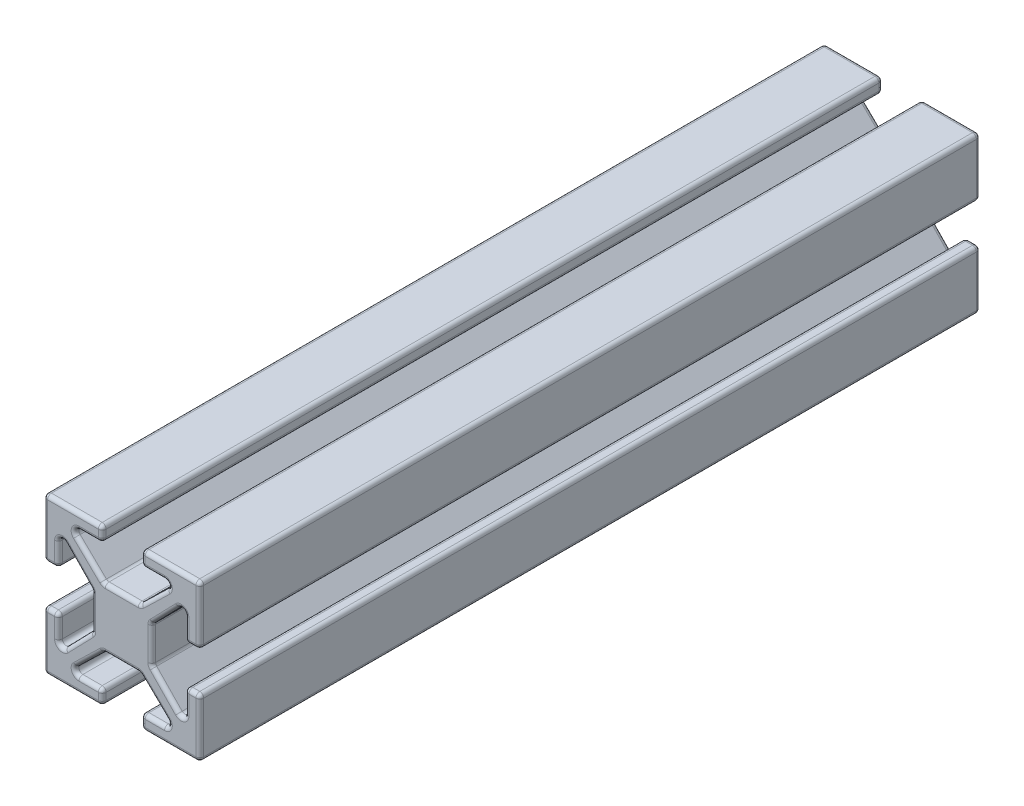
SolidWorks part; units mm, degrees
ref_plane "Front Plane" through (0, 0, 0) normal (0, 0, 1) x (1, 0, 0)
ref_plane "Top Plane" through (0, 0, 0) normal (0, 1, 0) x (1, 0, 0)
ref_plane "Right Plane" through (0, 0, 0) normal (1, 0, 0) x (0, 0, -1)
sketch "Sketch1" plane through (0, 0, 0) normal (0, 0, 1) x (1, 0, 0)
  line L0 (-5, 20) -> (-5, 16.2126)
  line L1 (-20, -20) -> (20, -20)
  line L2 (-20, -20) -> (-20, 20)
  line L3 (-20, 20) -> (20, 20)
  line L4 (20, -20) -> (20, 20)
  line L5 (-20, -20) -> (20, 20) construction
  line L6 (-20, 20) -> (20, -20) construction
  line L7 (-5, 16.2126) -> (-13.4323, 16.2126)
  line L8 (-13.4323, 16.2126) -> (-4.6312, 7.6894)
  line L9 (-4.6312, 7.6894) -> (0, 7.6894)
  line L10 (-7.6894, 4.6312) -> (-7.6894, 0)
  line L11 (-16.2126, 13.4323) -> (-7.6894, 4.6312)
  line L12 (-16.2126, 5) -> (-16.2126, 13.4323)
  line L13 (-20, 5) -> (-16.2126, 5)
  line L14 (0, 7.6894) -> (0, 16.8611) construction
  line L15 (0, 0) -> (-11.384, 0) construction
  line L16 (5, 20) -> (5, 16.2126)
  line L17 (5, 16.2126) -> (13.4323, 16.2126)
  line L18 (13.4323, 16.2126) -> (4.6312, 7.6894)
  line L19 (16.2126, 13.4323) -> (7.6894, 4.6312)
  line L20 (16.2126, 5) -> (16.2126, 13.4323)
  line L21 (20, 5) -> (16.2126, 5)
  line L22 (7.6894, 4.6312) -> (7.6894, 0)
  line L23 (4.6312, 7.6894) -> (0, 7.6894)
  line L24 (20, -5) -> (16.2126, -5)
  line L25 (16.2126, -5) -> (16.2126, -13.4323)
  line L26 (16.2126, -13.4323) -> (7.6894, -4.6312)
  line L27 (13.4323, -16.2126) -> (4.6312, -7.6894)
  line L28 (5, -16.2126) -> (13.4323, -16.2126)
  line L29 (5, -20) -> (5, -16.2126)
  line L30 (4.6312, -7.6894) -> (0, -7.6894)
  line L31 (7.6894, -4.6312) -> (7.6894, 0)
  line L32 (-5, -20) -> (-5, -16.2126)
  line L33 (-5, -16.2126) -> (-13.4323, -16.2126)
  line L34 (-13.4323, -16.2126) -> (-4.6312, -7.6894)
  line L35 (-16.2126, -13.4323) -> (-7.6894, -4.6312)
  line L36 (-16.2126, -5) -> (-16.2126, -13.4323)
  line L37 (-20, -5) -> (-16.2126, -5)
  line L38 (-7.6894, -4.6312) -> (-7.6894, 0)
  line L39 (-4.6312, -7.6894) -> (0, -7.6894)
  point P0 (0, 0)
  point P52 (0, 0)
  dimension "D1" = 40
  dimension "D2" = 40
  dimension "D4" = 15
  dimension "D3" = 4
extrude "Boss-Extrude1" add sketch "Sketch1" along normal blind 200 contours L34 L39 L30 L27 L28 L29 L1 L4 L24 L25 L26 L31 L22 L19 L20 L21 L3 L16 L17 L18 L23 L9 L8 L7 L0 L2 L13 L12 L11 L10 L38 L35 L36 L37 L32 L33 region at (0, 0, 0)
fillet "Fillet3" radius 1 108 edges at (-9.0317, -11.951, 0) (0, -7.6894, 0) (9.0317, -11.951, 0) (9.2161, -16.2126, 0) (5, -18.1063, 0) (12.5, -20, 0) (20, -12.5, 0) (18.1063, -5, 0) (16.2126, -9.2161, 0) (11.951, -9.0317, 0) (7.6894, 0, 0) (11.951, 9.0317, 0) (16.2126, 9.2161, 0) (18.1063, 5, 0) (20, 12.5, 0) (5, 18.1063, 0) (9.2161, 16.2126, 0) (9.0317, 11.951, 0) (0, 7.6894, 0) (-9.0317, 11.951, 0) (-9.2161, 16.2126, 0) (-5, 18.1063, 0) (-12.5, 20, 0) (-20, 12.5, 0) (-18.1063, 5, 0) (-16.2126, 9.2161, 0) (-11.951, 9.0317, 0) (-7.6894, 0, 0) (-11.951, -9.0317, 0) (-16.2126, -9.2161, 0) (-18.1063, -5, 0) (-20, -12.5, 0) (-12.5, -20, 0) (-5, -18.1063, 0) (-9.2161, -16.2126, 0) (-9.0317, -11.951, 200) (0, -7.6894, 200) (9.0317, -11.951, 200) (9.2161, -16.2126, 200) (5, -18.1063, 200) (12.5, -20, 200) (20, -12.5, 200) (18.1063, -5, 200) (16.2126, -9.2161, 200) (11.951, -9.0317, 200) (7.6894, 0, 200) (11.951, 9.0317, 200) (16.2126, 9.2161, 200) (18.1063, 5, 200) (20, 12.5, 200) (12.5, 20, 200) (5, 18.1063, 200) (9.2161, 16.2126, 200) (9.0317, 11.951, 200) (0, 7.6894, 200) (-9.0317, 11.951, 200) (-9.2161, 16.2126, 200) (-5, 18.1063, 200) (-12.5, 20, 200) (-20, 12.5, 200) (-18.1063, 5, 200) (-16.2126, 9.2161, 200) (-11.951, 9.0317, 200) (-7.6894, 0, 200) (-11.951, -9.0317, 200) (-16.2126, -9.2161, 200) (-18.1063, -5, 200) (-20, -12.5, 200) (-12.5, -20, 200) (-5, -18.1063, 200) (-9.2161, -16.2126, 200) (-13.4323, -16.2126, 100) (-5, -16.2126, 100) (-5, -20, 100) (-20, -20, 100) (-20, -5, 100) (-16.2126, -5, 100) (-16.2126, -13.4323, 100) (-7.6894, -4.6312, 100) (-7.6894, 4.6312, 100) (-16.2126, 13.4323, 100) (-16.2126, 5, 100) (-20, 5, 100) (-20, 20, 100) (-5, 20, 100) (-5, 16.2126, 100) (-13.4323, 16.2126, 100) (-4.6312, 7.6894, 100) (4.6312, 7.6894, 100) (13.4323, 16.2126, 100) (5, 16.2126, 100) (5, 20, 100) (20, 20, 100) (20, 5, 100) (16.2126, 5, 100) (16.2126, 13.4323, 100) (7.6894, 4.6312, 100) (7.6894, -4.6312, 100) (16.2126, -13.4323, 100) (16.2126, -5, 100) (20, -5, 100) (20, -20, 100) (5, -20, 100) (5, -16.2126, 100) (13.4323, -16.2126, 100) (4.6312, -7.6894, 100) (-4.6312, -7.6894, 100) (12.5, 20, 0)
